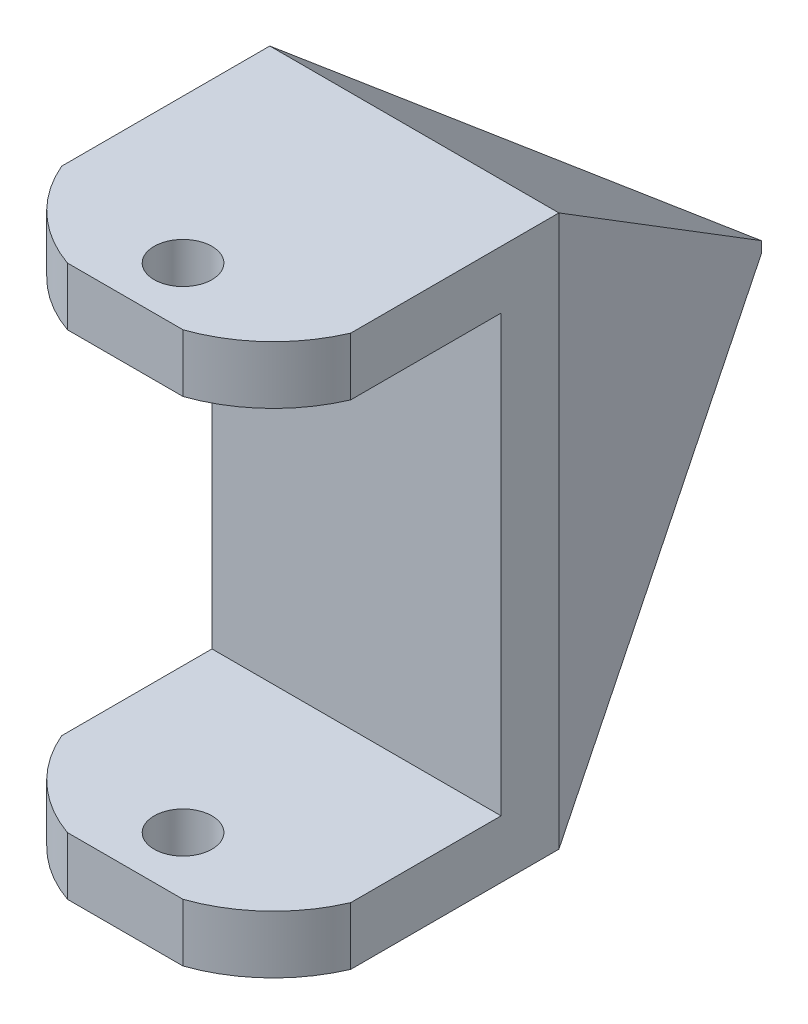
SolidWorks part; units mm, degrees
ref_plane "Front Plane" through (0, 0, 0) normal (0, 0, 1) x (1, 0, 0)
ref_plane "Top Plane" through (0, 0, 0) normal (0, 1, 0) x (1, 0, 0)
ref_plane "Right Plane" through (0, 0, 0) normal (1, 0, 0) x (0, 0, -1)
sketch "Sketch1" plane through (0, 0, 0) normal (0, 1, 0) x (1, 0, 0)
  line L1 (-5, 0) -> (5, 0)
  line L2 (-12.5, 7) -> (-12.5, 25)
  line L3 (-12.5, 25) -> (12.5, 25)
  line L4 (12.5, 7) -> (12.5, 25)
  arc A0 (5, 0) -> (12.5, 7) centre (0.8167, 12) ccw
  arc A1 (-5, 0) -> (-12.5, 7) centre (-0.8167, 12) cw
  circle A3 centre (0, 5) radius 2.5
  point P5 (0, 0)
  point P12 (-12.5, 0)
  point P13 (0, 25)
  dimension "D3" = 10
  dimension "D4" = 20
  dimension "D6" = 5
  dimension "D1" = 25
  dimension "D2" = 25
  dimension "D5" = 13
  dimension "D7" = 7
extrude "Boss-Extrude1" add sketch "Sketch1" along normal blind 47.65
sketch "Sketch2" plane through (-12.5, 0, 0) normal (-1, 0, 0) x (0, 0, 1)
  line L0 (0, 47.65) -> (0, 0) construction
  line L1 (0, 5) -> (-20, 5)
  line L2 (0, 5) -> (0, 42.65)
  line L3 (0, 42.65) -> (-20, 42.65)
  line L4 (-20, 5) -> (-20, 42.65)
  point P6 (0, 23.825)
  point P7 (0, 23.825)
  dimension "D1" = 37.65
  dimension "D2" = 20
extrude "Cut-Extrude1" cut sketch "Sketch2" against normal through all
ref_plane "B mid plane" through (0, 23.825, 0) normal (0, -1, 0) x (-1, 0, 0)
sketch "Sketch3" plane through (0, 47.65, 0) normal (0, 1, 0) x (1, 0, 0)
  line L0 (-12.5, 25) -> (0, 55)
  line L1 (0, 55) -> (12.5, 25)
  line L2 (12.5, 25) -> (-12.5, 25)
  point P5 (0, 0)
  point P6 (0, 25)
  dimension "D1" = 30
extrude "Boss-Extrude2" add sketch "Sketch3" against normal up to surface (47.65 mm away) up to face at (0, 0, -10.4032)
sketch "Sketch4" plane through (0, 0, -4.2308) normal (-1, 0, 0) x (0, 0, 1)
  line L0 (-50.7692, 47.65) -> (-50.7692, 24.325)
  line L1 (-50.7692, 0) -> (-50.7692, 47.65) construction
  line L2 (-50.7692, 24.325) -> (-20.7692, 47.65)
  line L3 (-20.7692, 47.65) -> (-50.7692, 47.65)
  line L4 (-50.7692, 0) -> (-50.7692, 23.325)
  line L5 (-50.7692, 23.325) -> (-20.7692, 0)
  line L6 (-20.7692, 0) -> (-50.7692, 0)
  line L8 (-9.5192, 23.825) -> (17.9808, 23.825) construction
  point P10 (0, 0)
  point P15 (0, 0)
  dimension "D1" = 1
  dimension "D2" = 0.5
extrude "Cut-Extrude2" cut sketch "Sketch4" against normal through all both and the other way through all
